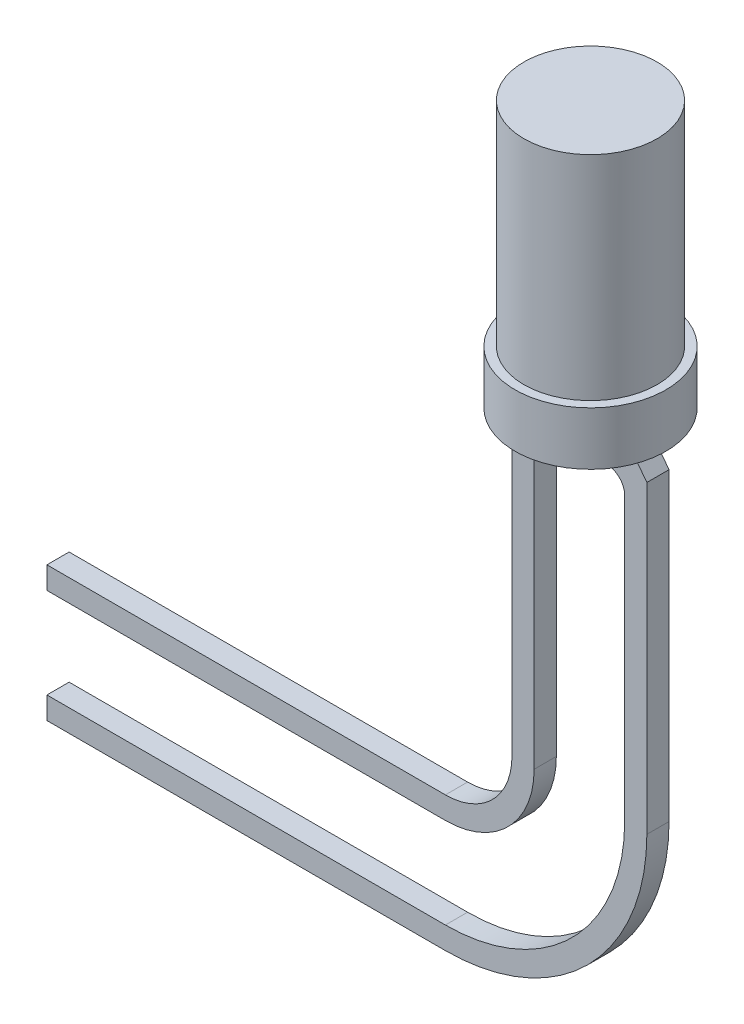
SolidWorks part; units mm, degrees
material "ABS PC"
ref_plane "Face" through (0, 0, 0) normal (0, 0, 1) x (1, 0, 0)
ref_plane "Dessus" through (0, 0, 0) normal (0, 1, 0) x (1, 0, 0)
ref_plane "Droite" through (0, 0, 0) normal (1, 0, 0) x (0, 0, -1)
sketch "Esquisse1" plane through (0, 0, 0) normal (0, 1, 0) x (1, 0, 0)
  circle A0 centre (0, 0) radius 1.5
  dimension "D1" = 3
extrude "Boss.-Extru.1" add sketch "Esquisse1" against normal blind 4.8
sketch "Esquisse2" plane through (0, -4.8, 0) normal (0, -1, 0) x (1, 0, 0)
  circle A0 centre (0, 0) radius 1.7
  dimension "D1" = 3.4
extrude "Boss.-Extru.2" add sketch "Esquisse2" along normal blind 1.2
sketch "Esquisse3" plane through (0, 0, 0) normal (0, 0, 1) x (1, 0, 0)
  line L0 (0, -6) -> (0, -13.3988) construction
  line L1 (-1.7, -6) -> (1.7, -6) construction
  line L2 (0.5, -6) -> (0.5, -6.6725)
  line L3 (0.5, -6.6725) -> (0.62, -6.6725)
  line L4 (1.02, -7.0725) -> (1.02, -13.4396)
  line L5 (-1.0841, -6) -> (-0.5, -6)
  line L6 (1.52, -13.4396) -> (1.52, -6.5725)
  line L7 (1.52, -6.5725) -> (1.0841, -6)
  line L8 (1.0841, -6) -> (0.5, -6)
  line L9 (-1.52, -6.5725) -> (-1.0841, -6)
  line L10 (-1.52, -13.4396) -> (-1.52, -6.5725)
  line L11 (-1.02, -7.0725) -> (-1.02, -13.4396)
  line L12 (-0.5, -6.6725) -> (-0.62, -6.6725)
  line L13 (-0.5, -6) -> (-0.5, -6.6725)
  line L14 (-3.02, -15.4396) -> (-12, -15.4396)
  line L15 (-12, -15.4396) -> (-12, -14.9396)
  line L16 (-12, -14.9396) -> (-3.02, -14.9396)
  line L17 (-3.02, -17.9796) -> (-12, -17.9796)
  line L18 (-12, -17.9796) -> (-12, -17.4796)
  line L19 (-12, -17.4796) -> (-3.02, -17.4796)
  arc A0 (0.62, -6.6725) -> (1.02, -7.0725) centre (0.62, -7.0725) cw
  arc A1 (-0.62, -6.6725) -> (-1.02, -7.0725) centre (-0.62, -7.0725) ccw
  arc A2 (-1.02, -13.4396) -> (-3.02, -15.4396) centre (-3.02, -13.4396) cw
  arc A3 (-3.02, -14.9396) -> (-1.52, -13.4396) centre (-3.02, -13.4396) ccw
  arc A4 (1.02, -13.4396) -> (-3.02, -17.4796) centre (-3.02, -13.4396) cw
  arc A5 (1.52, -13.4396) -> (-3.02, -17.9796) centre (-3.02, -13.4396) cw
  dimension "D1" = 0.4
  dimension "D6" = 1.5
  dimension "D2" = 0.5
  dimension "D3" = 1.02
  dimension "D4" = 1
  dimension "D5" = 12
extrude "Boss.-Extru.3" add sketch "Esquisse3" along normal blind 0.25 and the other way blind 0.25
